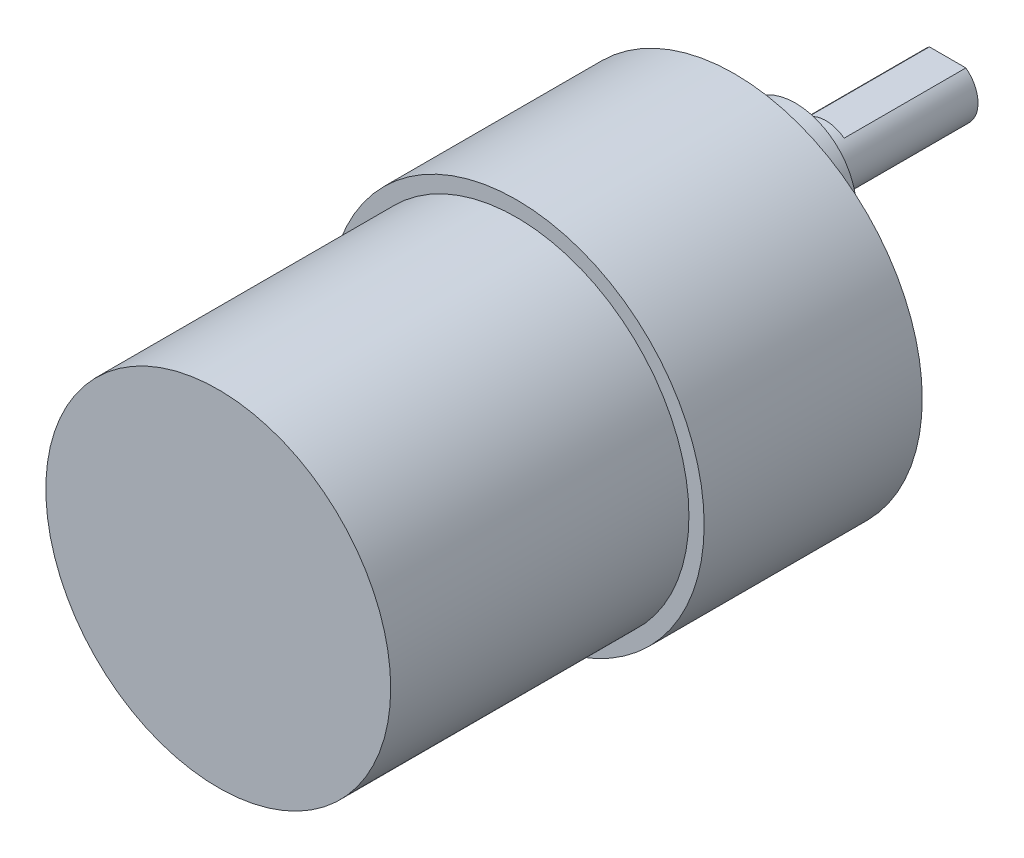
SolidWorks part; units mm, degrees
ref_plane "前视基准面" through (0, 0, 0) normal (0, 0, 1) x (1, 0, 0)
ref_plane "上视基准面" through (0, 0, 0) normal (0, 1, 0) x (1, 0, 0)
ref_plane "右视基准面" through (0, 0, 0) normal (1, 0, 0) x (0, 0, -1)
sketch "草图1" plane through (0, 0, 0) normal (0, 0, 1) x (1, 0, 0)
  circle A0 centre (0, 0) radius 18.5
  point P5 (0, 0)
extrude "凸台-拉伸1" add sketch "草图1" along normal blind 21.5 contours A0
sketch "草图2" plane through (0, 0, 21.5) normal (0, 0, 1) x (1, 0, 0)
  circle A0 centre (0, 0) radius 17
extrude "凸台-拉伸2" add sketch "草图2" along normal blind 29.4
sketch "草图3" plane through (0, 0, 0) normal (0, 0, -1) x (-1, 0, 0)
  line L0 (0, 0) -> (0, 7)
  arc A0 (-11.3605, 5.2143) -> (11.3605, 5.2143) centre (0, 7) ccw
  circle A1 centre (0, 0) radius 18.5
  arc A2 (-11.3605, 5.2143) -> (11.3605, 5.2143) centre (0, 0) ccw
extrude "切除-拉伸1" cut sketch "草图3" against normal blind 1 contours A0 A2 region at (0, -5.6946, 0)
sketch "草图4" plane through (0, 0, 0) normal (0, 0, -1) x (-1, 0, 0)
  circle A0 centre (0, 7) radius 6
extrude "凸台-拉伸3" add sketch "草图4" along normal blind 6
sketch "草图5" plane through (0, 0, -6) normal (0, 0, -1) x (-1, 0, 0)
  circle A0 centre (0, 7) radius 3
extrude "凸台-拉伸4" add sketch "草图5" along normal blind 15
sketch "草图6" plane through (0, 0, -21) normal (0, 0, -1) x (-1, 0, 0)
  line L2 (0, 9.4) -> (1.8, 9.4)
  line L3 (0, 9.4) -> (-1.8, 9.4)
  circle A0 centre (0, 7) radius 3 construction
  arc A1 (1.8, 9.4) -> (-1.8, 9.4) centre (0, 7) ccw
extrude "切除-拉伸2" cut sketch "草图6" against normal blind 12
sketch "草图7" plane through (0, 0, 0) normal (0, 0, -1) x (-1, 0, 0)
  circle A2 centre (15.5, 0) radius 1.5
  circle A3 centre (-15.5, 0) radius 1.5
  circle A4 centre (-7.75, -13.4234) radius 1.5
  circle A6 centre (7.75, 13.4234) radius 1.5
  circle A7 centre (-7.75, 13.4234) radius 1.5
  circle A9 centre (7.75, -13.4234) radius 1.5
  point P21 (0, 0)
  dimension "D1" = 3
extrude "切除-拉伸3" cut sketch "草图7" against normal blind 5
sketch "草图8" plane through (0, 0, 0) normal (0, 0, -1) x (-1, 0, 0)
  circle A0 centre (0, -15.5) radius 2
  circle A1 centre (-13.4234, 7.75) radius 2
  circle A2 centre (13.4234, 7.75) radius 2
  point P9 (0, 0)
  dimension "D1" = 3
extrude "切除-拉伸4" cut sketch "草图8" against normal blind 1
